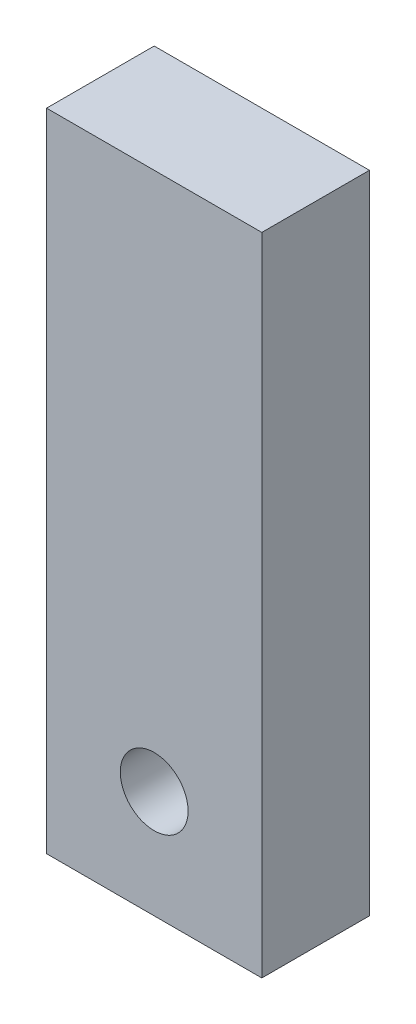
SolidWorks part; units mm, degrees
ref_plane "Front Plane" through (0, 0, 0) normal (0, 0, 1) x (1, 0, 0)
ref_plane "Top Plane" through (0, 0, 0) normal (0, 1, 0) x (1, 0, 0)
ref_plane "Right Plane" through (0, 0, 0) normal (1, 0, 0) x (0, 0, -1)
sketch "Sketch1" plane through (0, 0, 0) normal (0, 0, 1) x (1, 0, 0)
  line L0 (55, 0) -> (-55, 0) construction
  line L1 (-12.7, -38.1) -> (12.7, -38.1)
  line L2 (-12.7, -38.1) -> (-12.7, 38.1)
  line L3 (-12.7, 38.1) -> (12.7, 38.1)
  line L4 (12.7, -38.1) -> (12.7, 38.1)
  line L5 (-12.7, -38.1) -> (12.7, 38.1) construction
  line L6 (-12.7, 38.1) -> (12.7, -38.1) construction
  line L7 (-12.7, 38.1) -> (12.7, 38.1)
  line L8 (-12.7, 38.1) -> (-12.7, 44.45)
  line L9 (-12.7, 44.45) -> (12.7, 44.45)
  line L10 (12.7, 38.1) -> (12.7, 44.45)
  line L11 (-12.7, -44.45) -> (12.7, -44.45)
  line L12 (12.7, -38.1) -> (12.7, -44.45)
  line L13 (-12.7, -38.1) -> (12.7, -38.1)
  line L14 (-12.7, -38.1) -> (-12.7, -44.45)
  point P0 (0, 0)
  point P10 (0, 44.45)
  point P11 (0, 38.1)
  point P18 (0, -38.1)
  point P19 (0, -44.45)
  dimension "D1" = 25.4
  dimension "D2" = 76.2
  dimension "D3" = 25.4
  dimension "D4" = 6.35
extrude "Boss-Extrude1" add sketch "Sketch1" along normal blind 12.7 contours L1 L4 L3 L2 region at (0, 0, 0)
sketch "Sketch2" plane through (0, 0, 12.7) normal (0, 0, 1) x (1, 0, 0)
  line L8 (-12.7, -38.1) -> (12.7, -38.1) construction
  circle A1 centre (0, -25.4) radius 4
  dimension "D2" = 12.7
  dimension "D1" = 8
extrude "Cut-Extrude1" cut sketch "Sketch2" against normal through all
